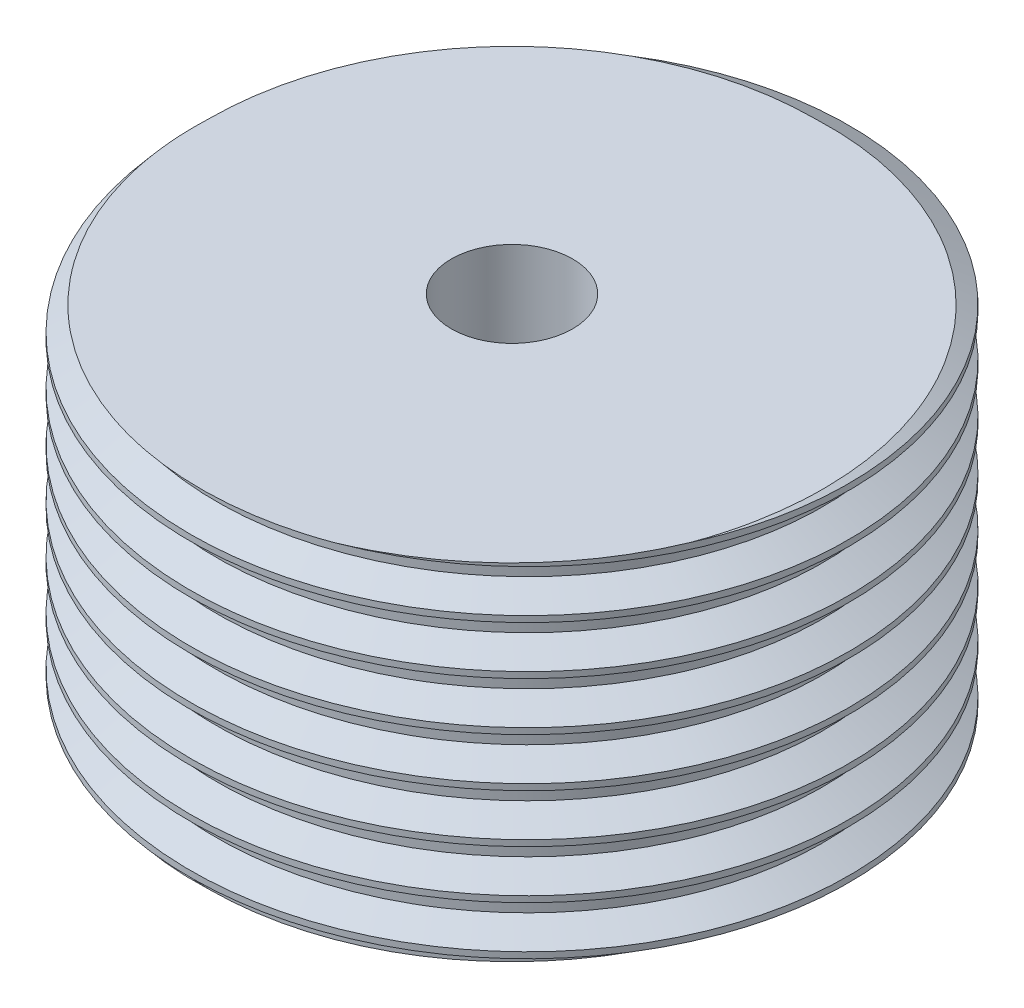
SolidWorks part; units mm, degrees
ref_plane "Alzado" through (0, 0, 0) normal (0, 0, 1) x (1, 0, 0)
ref_plane "Planta" through (0, 0, 0) normal (0, 1, 0) x (1, 0, 0)
ref_plane "Vista lateral" through (0, 0, 0) normal (1, 0, 0) x (0, 0, -1)
sketch "Croquis1" plane through (0, 0, 0) normal (0, 1, 0) x (1, 0, 0)
  circle A0 centre (0, 0) radius 12.5
  dimension "D1" = 25
extrude "Saliente-Extruir1" add sketch "Croquis1" along normal blind 15
thread "Rosca1" start angle 0, offset 2, length 0, pitch 2, diameter 25
ref_plane "Plano1" through (12.5, -2, 0) normal (0, 0, 1) x (1, 0, 0)
sketch "Perfil de rosca1" plane through (12.5, -2, 0) normal (0, 0, 1) x (1, 0, 0)
  line L0 (0, 0) -> (0, 2) construction
  line L1 (0, 0) -> (1.0825, 0.625)
  line L2 (1.0825, 0.625) -> (1.0825, 0.875)
  line L3 (1.0825, 0.875) -> (0, 1.5)
  line L4 (1.0825, 0.75) -> (0, 0.75) construction
  line L11 (0, 0) -> (0, 1.5)
  point P2 (0, 0)
  dimension "Pitch" = 2
  dimension "Profile_Angle" = 60
  dimension "Profile_Land" = 0.25
  dimension "Profile_Height" = 1.0825
sketch "Croquis4" plane through (0, 0, 0) normal (0, -1, 0) x (1, 0, 0)
  circle A0 centre (0, 0) radius 2.5
  dimension "D1" = 5
extrude "Cortar-Extruir1" cut sketch "Croquis4" against normal through all
